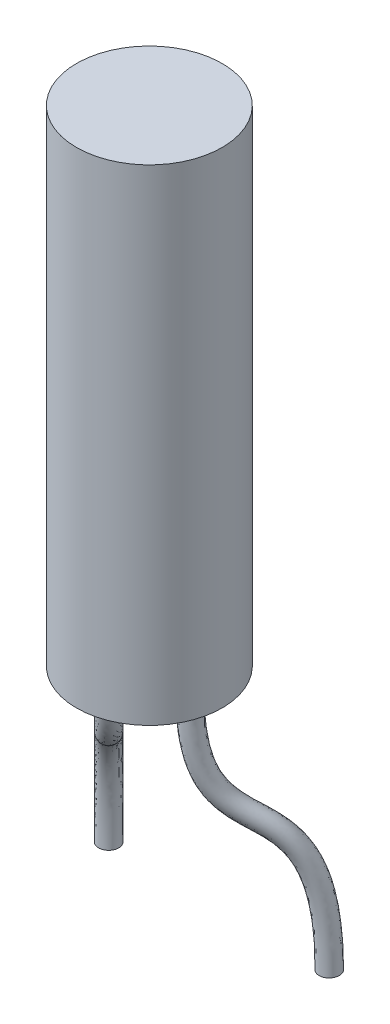
SolidWorks part; units mm, degrees
ref_plane "Front Plane" through (0, 0, 0) normal (0, 0, 1) x (1, 0, 0)
ref_plane "Top Plane" through (0, 0, 0) normal (0, 1, 0) x (1, 0, 0)
ref_plane "Right Plane" through (0, 0, 0) normal (1, 0, 0) x (0, 0, -1)
sketch "Sketch1" plane through (0, 0, 0) normal (0, 1, 0) x (1, 0, 0)
  circle A0 centre (0, 0) radius 0.9
  dimension "D1" = 1.8
extrude "Boss-Extrude1" add sketch "Sketch1" along normal blind 6
ref_axis "Axis1" through (0, 6.3, 0) along (0, -1, 0)
ref_plane "A" through (0, 0, 0) normal (-0.7071, 0, 0.7071) x (0, -1, 0)
ref_plane "B" through (0, 0, 0) normal (-0.7071, 0, -0.7071) x (0, -1, 0)
ref_plane "A1" through (-0.251, 0, 0.251) normal (-0.7071, 0, 0.7071) x (0, -1, 0)
ref_axis "Ax-A" through (-0.502, -0.63, 0) along (0, 1, 0)
ref_plane "B1" through (0.251, 0, 0.251) normal (-0.7071, 0, -0.7071) x (0, -1, 0)
ref_axis "Ax-B" through (0.502, 6.3, 0) along (0, -1, 0)
sketch "Sketch4" plane through (-0.251, 0, 0.251) normal (-0.7071, 0, 0.7071) x (0, -1, 0)
  line L0 (0, -0.9) -> (0, 0.9) construction
  line L1 (0.63, -0.355) -> (-6.63, -0.355) construction
  spline S0 degree 3 poles (0, -0.355) (2.0249, -0.3433) (0.6418, -1.5743) (3, -1.5788) knots 0 0 0 0 1 1 1 1
  dimension "D1" = 3
sketch "Sketch6" plane through (0.251, 0, 0.251) normal (-0.7071, 0, -0.7071) x (0, -1, 0)
  line L0 (-6.3, -0.355) -> (0.3, -0.355) construction
  line L1 (0, -0.9) -> (0, 0.9) construction
  spline S0 degree 3 poles (0, -0.355) (2.0249, -0.3433) (0.6418, -1.5681) (3, -1.5725) knots 0 0 0 0 1 1 1 1
sketch "Sketch7" plane through (0, 0, 0) normal (0, -1, 0) x (1, 0, 0)
  circle A0 centre (-0.502, 0) radius 0.125
  dimension "D1" = 0.25
sketch "Sketch8" plane through (0, 0, 0) normal (0, -1, 0) x (1, 0, 0)
  circle A0 centre (0.502, 0) radius 0.125
  dimension "D1" = 0.25
sweep "Sweep1" add profiles "Sketch7" path "Sketch4"
sweep "Sweep2" add profiles "Sketch8" path "Sketch6"
